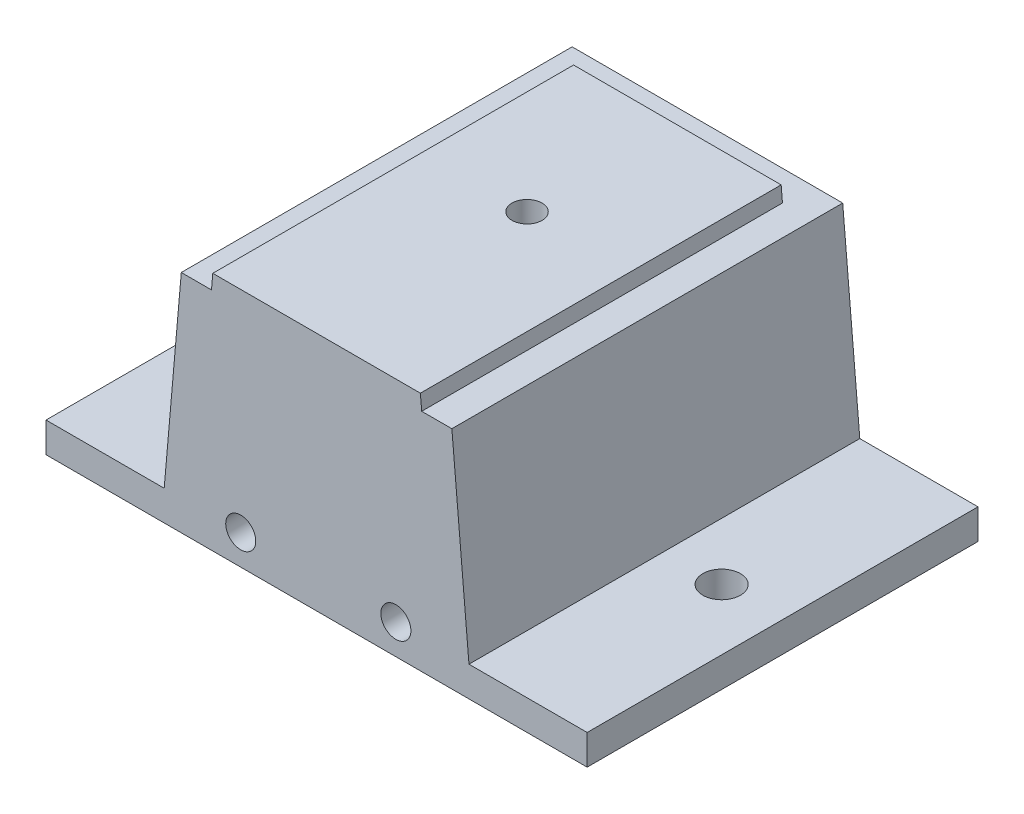
SolidWorks part; units mm, degrees
material "6061 Alloy"
ref_plane "Front Plane" through (0, 0, 0) normal (0, 0, 1) x (1, 0, 0)
ref_plane "Top Plane" through (0, 0, 0) normal (0, 1, 0) x (1, 0, 0)
ref_plane "Right Plane" through (0, 0, 0) normal (1, 0, 0) x (0, 0, -1)
sketch "Sketch1" plane through (0, 0, 0) normal (0, 0, 1) x (1, 0, 0)
  line L0 (0, 0) -> (0, 65.9076) construction
  line L1 (57.15, 0) -> (-57.15, 0)
  line L2 (-57.15, 0) -> (-57.15, 6.35)
  line L3 (-57.15, 6.35) -> (-32.1861, 6.35)
  line L4 (-32.1861, 6.35) -> (-28.575, 47.625)
  line L5 (-21.923, 50.8) -> (21.923, 50.8)
  line L6 (57.15, 0) -> (57.15, 6.35)
  line L7 (57.15, 6.35) -> (32.1861, 6.35)
  line L8 (32.1861, 6.35) -> (28.575, 47.625)
  line L9 (-28.575, 47.625) -> (-22.2007, 47.625)
  line L10 (-22.2007, 47.625) -> (-21.923, 50.8)
  line L11 (21.923, 50.8) -> (22.2007, 47.625)
  line L12 (22.2007, 47.625) -> (28.575, 47.625)
  point P12 (0, 50.8)
  point P15 (-22.0619, 49.2125)
  dimension "D3" = 50.8
  dimension "D4" = 95
  dimension "D6" = 3.175
extrude "Boss-Extrude1" add sketch "Sketch1" along normal mid plane 82.55
shell "Shell1" thickness 6.35 removed face at (0, 0, 0)
sketch "Sketch7" plane through (0, 0, 0) normal (1, 0, 0) x (0, 0, -1)
  line L0 (41.275, 47.625) -> (34.925, 47.625)
  line L2 (-41.275, 47.625) -> (41.275, 47.625) construction
  line L3 (34.925, 47.625) -> (34.925, 50.8)
  line L4 (-41.275, 50.8) -> (41.275, 50.8) construction
  line L5 (34.925, 50.8) -> (41.275, 50.8)
  line L6 (41.275, 50.8) -> (41.275, 47.625)
  dimension "D1" = 6.35
extrude "Cut-Extrude2" cut sketch "Sketch7" against normal through all both and the other way through all
sketch "Sketch8" plane through (0, 0, -50.8) normal (0, 1, 0) x (1, 0, 0)
  line L4 (0, -78.74) -> (0, -22.86) construction
  circle A1 centre (44.2781, -50.8) radius 3.9687
  circle A2 centre (-44.2781, -50.8) radius 3.9687
  dimension "D5" = 7.9375
extrude "Cut-Extrude3" cut sketch "Sketch8" along normal through all
hole_wizard "1/4 (0.25) Diameter Hole1" positions "Sketch9" profile "Sketch10" hole size "1/4" standard "ANSI Inch" end condition up to next
sketch "Sketch9" plane through (0, 50.8, 0) normal (0, 1, 0) x (1, 0, 0)
  line L0 (0, 0) -> (0, 25.0279) construction
  point P0 (0, 3.175)
sketch "Sketch10" plane through (0, 50.8, -3.175) normal (1, 0, 0) x (0, 0, 1)
  line L0 (0, 0) -> (0, 6.35)
  line L1 (0, 6.35) -> (3.175, 6.35)
  line L2 (3.175, 6.35) -> (3.175, 0)
  line L5 (3.175, 0) -> (0, 0)
  line L11 (0, -6.35) -> (0, 107.95) construction
  dimension "Thru Hole Dia." = 6.35
  dimension "Thru Hole Depth" = 6.35
hole_wizard "1/4 (0.25) Diameter Hole2" positions "Sketch11" profile "Sketch12" hole size "1/4" standard "ANSI Inch" end condition through all
sketch "Sketch11" plane through (0, 0, -41.275) normal (0, 0, -1) x (-1, 0, 0)
  point P0 (-16.7468, 6.35)
  point P3 (16.0172, 6.35)
sketch "Sketch12" plane through (16.7468, 6.35, -41.275) normal (1, 0, 0) x (0, 1, 0)
  line L0 (0, 0) -> (0, 82.55)
  line L1 (0, 82.55) -> (3.175, 82.55)
  line L2 (3.175, 82.55) -> (3.175, 0)
  line L5 (3.175, 0) -> (0, 0)
  line L11 (0, -6.35) -> (0, 107.95) construction
  dimension "Thru Hole Dia." = 6.35
  dimension "Thru Hole Depth" = 82.55
equation "\"BedBaseDraftAngle\"=95"
equation "\"D4@Sketch1\"=\"BedBaseDraftAngle\""
